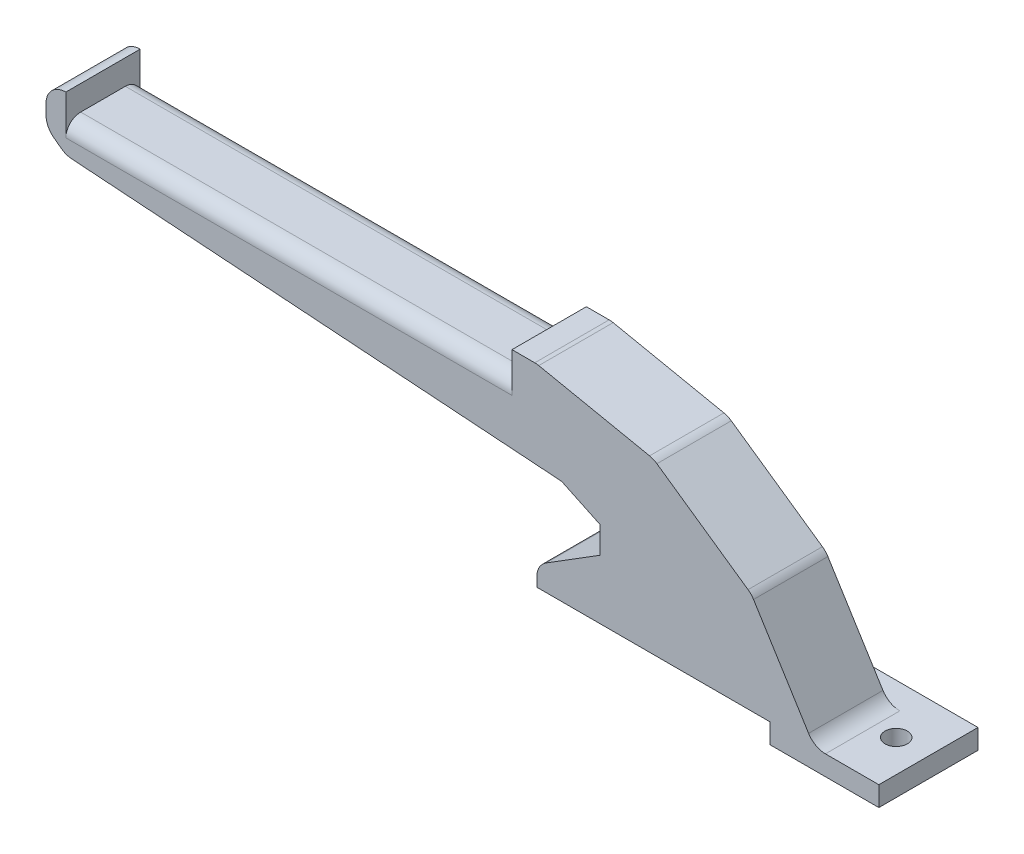
SolidWorks part; units mm, degrees
ref_plane "Plan de face" through (0, 0, 0) normal (0, 0, 1) x (1, 0, 0)
ref_plane "Plan de dessus" through (0, 0, 0) normal (0, 1, 0) x (1, 0, 0)
ref_plane "Plan de droite" through (0, 0, 0) normal (1, 0, 0) x (0, 0, -1)
sketch "Esquisse1" plane through (0, 0, 0) normal (0, 0, 1) x (1, 0, 0)
  line L0 (0, 0) -> (-22, 0)
  line L1 (-22, 0) -> (-22, 4)
  line L2 (-22, 4) -> (-69, 4)
  line L3 (-69, 4) -> (-69, 8)
  line L4 (0, 0) -> (0, 4)
  line L5 (0, 4) -> (-13, 4)
  line L6 (-69, 8) -> (-69, 43) construction
  line L7 (-69, 43) -> (-74, 43)
  line L8 (-74, 43) -> (-74, 38)
  line L9 (-74, 38) -> (-164, 38)
  line L10 (-164, 38) -> (-164, 43)
  line L11 (-164, 43) -> (-168, 43)
  line L12 (-168, 43) -> (-168, 35)
  line L13 (-168, 35) -> (-164, 32)
  line L14 (-164, 32) -> (-64, 25)
  line L15 (-13, 4) -> (-25.7111, 24.4139)
  line L16 (-25.7111, 24.4139) -> (-45.4449, 38.1571)
  line L17 (-45.4449, 38.1571) -> (-69, 43)
  line L18 (-64, 25) -> (-56.2602, 21.3381)
  line L19 (-56.2602, 21.3381) -> (-56.2602, 15.9502)
  line L20 (-56.2602, 15.9502) -> (-69, 8)
  arc A0 (-69, 43) -> (-13, 4) centre (-69, -16.7051) cw construction
  spline S0 degree 3 poles (-64, 25) (-48.4213, 23.9095) (-60.1317, 9.5266) (-69, 8) knots 0 0 0 0 1 1 1 1 construction
  dimension "D15" = 10
  dimension "D1" = 4
  dimension "D2" = 22
  dimension "D3" = 13
  dimension "D4" = 47
  dimension "D5" = 43
  dimension "D6" = 5
  dimension "D7" = 4
  dimension "D8" = 5
  dimension "D9" = 5
  dimension "D10" = 4
  dimension "D11" = 11
  dimension "D12" = 8
  dimension "D13" = 4
  dimension "D14" = 18
  dimension "D16" = 90
extrude "Boss.-Extru.1" add sketch "Esquisse1" along normal blind 15
fillet "Congé1" radius 3 2 edges at (-119, 38, 0) (-119, 38, 15)
fillet "Congé2" radius 4 8 edges at (-168, 35, 7.5) (-164, 32, 7.5) (-168, 43, 7.5) (-69, 43, 7.5) (-45.4449, 38.1571, 7.5) (-25.7111, 24.4139, 7.5) (-69, 8, 7.5) (-13, 4, 7.5)
sketch "Esquisse2" plane through (0, 0, 0) normal (0, 0, -1) x (-1, 0, 0)
  line L1 (0, 4) -> (22, 4)
  line L2 (0, 4) -> (0, 0)
  line L3 (0, 0) -> (22, 0)
  line L4 (22, 4) -> (22, 0)
extrude "Boss.-Extru.2" add sketch "Esquisse2" along normal blind 5
hole_wizard "Dégagement M41" positions "Esquisse4" profile "Esquisse3" hole size "M4" standard "Din"
sketch "Esquisse4" plane through (0, 4, 0) normal (0, 1, 0) x (1, 0, 0)
  line L0 (0, -15) -> (-10.7786, -15) construction
  line L1 (0, -15) -> (0, 5) construction
  point P0 (-6.5, -5)
  dimension "D1" = 10
  dimension "D2" = 6.5
sketch "Esquisse3" plane through (-6.5, 4, 5) normal (1, 0, 0) x (0, 0, 1)
  line L0 (0, 0) -> (0, 16)
  line L1 (0, 16) -> (2.25, 16)
  line L2 (2.25, 16) -> (2.25, 0)
  line L5 (2.25, 0) -> (0, 0)
  line L10 (0, 16) -> (-2.25, 16) construction
  line L11 (0, -6.35) -> (0, 107.95) construction
  dimension "Diamètre du perçage" = 4.5
  dimension "Profondeur du perçage" = 16
  dimension "Angle de pointe" = 180
